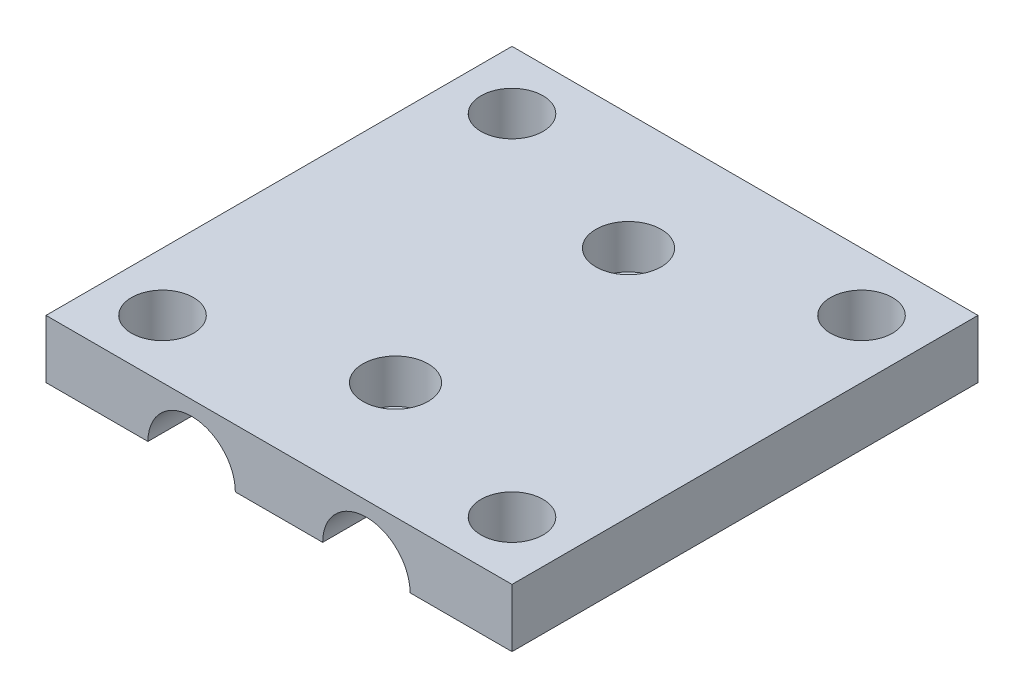
SolidWorks part; units mm, degrees
ref_plane "Front Plane" through (0, 0, 0) normal (0, 0, 1) x (1, 0, 0)
ref_plane "Top Plane" through (0, 0, 0) normal (0, 1, 0) x (1, 0, 0)
ref_plane "Right Plane" through (0, 0, 0) normal (1, 0, 0) x (0, 0, -1)
sketch "Sketch1" plane through (0, 0, 0) normal (0, 1, 0) x (1, 0, 0)
  line L1 (-25.4, 25.4) -> (25.4, 25.4)
  line L2 (-25.4, 25.4) -> (-25.4, -25.4)
  line L3 (-25.4, -25.4) -> (25.4, -25.4)
  line L4 (25.4, 25.4) -> (25.4, -25.4)
  dimension "D1" = 50.8
  dimension "D2" = 50.8
  dimension "D3" = 25.4
  dimension "D4" = 25.4
extrude "Boss-Extrude1" add sketch "Sketch1" along normal blind 6.35
sketch "Sketch2" plane through (0, 0, 25.4) normal (0, 0, 1) x (1, 0, 0)
  line L0 (-25.4, 0) -> (25.4, 0) construction
  circle A0 centre (-9.525, 0) radius 4.7625
  circle A1 centre (9.525, 0) radius 4.7625
  dimension "D1" = 9.525
  dimension "D2" = 9.525
  dimension "D3" = 9.525
  dimension "D4" = 9.525
extrude "Cut-Extrude1" cut sketch "Sketch2" against normal through all
hole_wizard "1/4 Clearance Hole1" positions "Sketch5" profile "Sketch4" hole size "1/4" standard "ANSI Inch" end condition through all
sketch "Sketch5" plane through (0, 6.35, 0) normal (0, 1, 0) x (1, 0, 0)
  point P0 (-19.05, -19.05)
  point P2 (-19.05, 19.05)
  point P4 (19.05, 19.05)
  point P6 (19.05, -19.05)
sketch "Sketch4" plane through (-19.05, 6.35, 19.05) normal (1, 0, 0) x (0, 0, 1)
  line L0 (0, 0) -> (0, 6.35)
  line L1 (0, 6.35) -> (3.3782, 6.35)
  line L2 (3.3782, 6.35) -> (3.3782, 0)
  line L5 (3.3782, 0) -> (0, 0)
  line L11 (0, -6.35) -> (0, 107.95) construction
  dimension "Thru Hole Dia." = 6.7564
  dimension "Thru Hole Depth" = 6.35
hole_wizard "#8 Clearance Hole1" positions "Sketch9" profile "Sketch8" hole size "#8" standard "ANSI Inch" end condition through all
sketch "Sketch9" plane through (0, 6.35, 0) normal (0, 1, 0) x (1, 0, 0)
  point P0 (0, 12.7)
  point P2 (0, -12.7)
sketch "Sketch8" plane through (0, 6.35, -12.7) normal (1, 0, 0) x (0, 0, 1)
  line L0 (0, 0) -> (0, 6.35)
  line L1 (0, 6.35) -> (2.2479, 6.35)
  line L2 (2.2479, 6.35) -> (2.2479, 0)
  line L5 (2.2479, 0) -> (0, 0)
  line L11 (0, -6.35) -> (0, 107.95) construction
  dimension "Thru Hole Dia." = 4.4958
  dimension "Thru Hole Depth" = 6.35
sketch "Sketch10" plane through (0, 6.35, 0) normal (0, 1, 0) x (1, 0, 0)
  circle A0 centre (0, 12.7) radius 3.556
  circle A1 centre (0, -12.7) radius 3.556
  dimension "D1" = 7.112
  dimension "D2" = 7.112
extrude "Cut-Extrude2" cut sketch "Sketch10" against normal blind 4.7625
